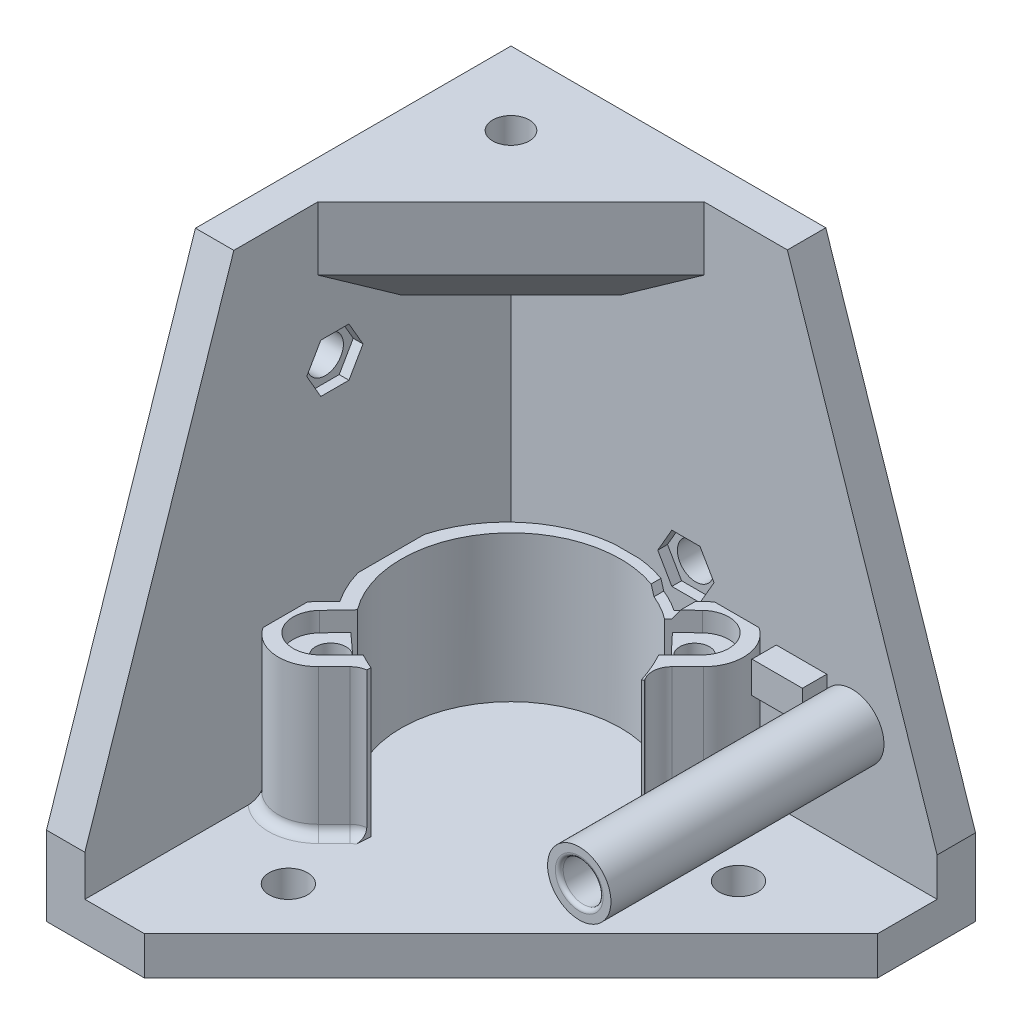
SolidWorks part; units mm, degrees
ref_plane "Front" through (0, 0, 0) normal (0, 0, 1) x (1, 0, 0)
ref_plane "Top" through (0, 0, 0) normal (0, 1, 0) x (1, 0, 0)
ref_plane "Right" through (0, 0, 0) normal (1, 0, 0) x (0, 0, -1)
sketch "Sketch1" plane through (0, 0, 0) normal (0, 1, 0) x (1, 0, 0)
  line L0 (0, 0) -> (0, 60.5)
  line L1 (0, -55) -> (0, 55) construction
  line L2 (0, 60.5) -> (60.5, 60.5)
  line L3 (60.5, 60.5) -> (60.5, 47.75)
  line L4 (60.5, 47.75) -> (12.75, 0)
  line L5 (-55, 0) -> (55, 0) construction
  line L6 (12.75, 0) -> (0, 0)
  dimension "D1" = 60.5
  dimension "D2" = 12.75
extrude "Boss-Extrude1" add sketch "Sketch1" along normal blind 5
sketch "Sketch4" plane through (0, 0, 0) normal (-1, 0, 0) x (0, 0, 1)
  line L0 (-60.5, 5) -> (-60.5, 68.5)
  line L1 (-60.5, 68.5) -> (-19.4, 68.5)
  line L2 (-19.4, 68.5) -> (0, 10.3086)
  line L3 (0, 10.3086) -> (0, 5)
  line L4 (0, -2.75) -> (0, 2.75) construction
  line L5 (-60.5, 5) -> (0, 5) construction
  line L6 (-60.5, 5) -> (0, 5)
  dimension "D1" = 63.5
  dimension "D2" = 41.1
  dimension "D3" = 61.34
extrude "Boss-Extrude2" add sketch "Sketch4" against normal blind 5
sketch "Sketch5" plane through (0, 0, -60.5) normal (0, 0, -1) x (-1, 0, 0)
  line L0 (0, 68.5) -> (-41, 68.5)
  line L1 (-41, 68.5) -> (-60.5, 10.0047)
  line L2 (-60.5, 10.0047) -> (-60.5, 5)
  line L6 (-60.5, 0) -> (0, 0)
  line L7 (0, 0) -> (0, 68.5)
  line L8 (0, 68.5) -> (-5, 68.5)
  line L9 (-5, 68.5) -> (-5, 5)
  line L10 (-5, 5) -> (-60.5, 5)
  line L11 (-60.5, 5) -> (-60.5, 0)
  line L12 (-60.5, 0) -> (0, 0)
  line L13 (0, 0) -> (0, 68.5)
  line L14 (0, 68.5) -> (-5, 68.5)
  line L15 (-5, 68.5) -> (-5, 5)
  line L16 (-5, 5) -> (-60.5, 5)
  line L17 (-60.5, 5) -> (-60.5, 0)
  line M13 (-5, 68.5) -> (-5, 5)
  line M14 (-5, 5) -> (-60.5, 5)
  dimension "D2" = 41
  dimension "D3" = 61.66
  dimension "D1" = 0
extrude "Boss-Extrude3" add sketch "Sketch5" against normal blind 5 contours L1 L2 L0 M14 M13 region at (28.6471, 34.3845, -60.5)
sketch "Sketch6" plane through (0, 5, 0) normal (0, 1, 0) x (1, 0, 0)
  line L0 (60.5, 60.5) -> (0, 60.5) construction
  line L4 (0, 19.4) -> (0, 0)
  line L5 (60.5, 55.5) -> (5, 55.5)
  line L6 (5, 55.5) -> (5, 0)
  line L7 (5, 0) -> (12.75, 0)
  line L8 (12.75, 0) -> (60.5, 47.75)
  line L9 (60.5, 47.75) -> (60.5, 55.5)
  line L10 (60.5, 55.5) -> (5, 55.5)
  line L11 (5, 55.5) -> (5, 0)
  line L12 (5, 0) -> (12.75, 0)
  line L13 (12.75, 0) -> (60.5, 47.75)
  line L14 (60.5, 47.75) -> (60.5, 55.5)
  line L15 (0, 0) -> (5, 0)
  line L16 (5, 0) -> (5, 19.4)
  line L17 (5, 19.4) -> (0, 19.4)
  line L18 (0, 19.4) -> (0, 0)
  line L19 (0, 0) -> (5, 0)
  line L20 (5, 0) -> (5, 19.4)
  line L21 (5, 19.4) -> (0, 19.4)
  line L24 (0, 60.5) -> (0, 19.4)
  line L25 (0, 19.4) -> (5, 19.4)
  line L26 (5, 19.4) -> (5, 55.5)
  line L27 (5, 55.5) -> (41, 55.5)
  line L28 (41, 55.5) -> (41, 60.5)
  line L29 (41, 60.5) -> (0, 60.5)
  line L30 (0, 60.5) -> (0, 19.4)
  line L31 (0, 19.4) -> (5, 19.4)
  line L32 (5, 19.4) -> (5, 55.5)
  line L33 (5, 55.5) -> (41, 55.5)
  line L34 (41, 55.5) -> (41, 60.5)
  line L35 (41, 60.5) -> (0, 60.5)
  circle A0 centre (16.5, 15) radius 2.5
  circle A1 centre (45.5, 44.625) radius 2.5
  dimension "D1" = 5
  dimension "D2" = 5
  dimension "D3" = 0
  dimension "D4" = 15
  dimension "D6" = 16.5
  dimension "D7" = 15
  dimension "D9" = 15.875
  dimension "D5" = 0
  dimension "D8" = 0
extrude "Cut-Extrude1" cut sketch "Sketch6" against normal through all contours A0 | A1 region at (16.5, 5, -15) region at (45.5, 5, -44.625)
sketch "Sketch9" plane through (0, 0, -55.5) normal (0, 0, 1) x (1, 0, 0)
  line L1 (5, 68.5) -> (5, 5) construction
  line L5 (0, 0) -> (60.5, 0)
  line L6 (0, 68.5) -> (0, 0)
  line L7 (41, 68.5) -> (0, 68.5)
  line L8 (60.5, 10.0047) -> (41, 68.5)
  line L9 (60.5, 0) -> (60.5, 10.0047)
  line L10 (0, 0) -> (60.5, 0)
  line L11 (0, 68.5) -> (0, 0)
  line L12 (41, 68.5) -> (0, 68.5)
  line L13 (60.5, 10.0047) -> (41, 68.5)
  line L14 (60.5, 0) -> (60.5, 10.0047)
  line L15 (49.45, 19.0462) -> (49.45, 11.3161) construction
  circle A0 centre (49.45, 19.0462) radius 4.1275
  circle A1 centre (49.45, 19.0462) radius 2.6035
  dimension "D2" = 5.207
  dimension "D3" = 1.524
  dimension "D4" = 49.4538
  dimension "D5" = 44.45
  dimension "D1" = 0
extrude "Boss-Extrude5" add sketch "Sketch9" along normal blind 35.56 contours A1 A0 region at (45.4392, 19.0462, -55.5)
fillet "Fillet1" radius 0.508 1 edges at (52.0535, 19.0462, -19.94)
sketch "Sketch14" plane through (0, 5, 0) normal (0, 1, 0) x (1, 0, 0)
  line L0 (13.4627, 27.5396) -> (14.7681, 26.7924)
  line L1 (12.75, 0) -> (60.5, 47.75) construction
  line L2 (36.625, 23.875) -> (5, 55.5) construction
  line L3 (5, 55.5) -> (60.5, 55.5) construction
  line L4 (32.9604, 47.0373) -> (33.7076, 45.7319)
  line L5 (14.8281, 26.8523) -> (11.8274, 23.8516)
  line L6 (6.723, 28.8027) -> (9.1327, 31.3641)
  line L7 (33.6477, 45.6719) -> (36.6484, 48.6726)
  line L8 (31.6973, 53.777) -> (29.1359, 51.3673)
  line L9 (15.0744, 24.4582) -> (13.006, 22.3898)
  line L10 (5.6561, 29.7396) -> (7.0609, 31.1444)
  line L11 (36.0418, 45.4256) -> (38.1102, 47.494)
  line L12 (30.7604, 54.8439) -> (28.83, 52.9135)
  line L13 (18.1324, 24.8665) -> (30.5234, 17.7734)
  line L14 (35.6335, 42.3676) -> (42.7266, 29.9766)
  line L15 (31.7409, 18.9909) -> (18.852, 25.7543)
  line L16 (41.5091, 28.7591) -> (34.7457, 41.648)
  line L17 (16.5689, 25.6946) -> (16.5343, 25.1798)
  line L18 (34.7457, 41.648) -> (35.7996, 42.0774)
  circle A0 centre (20.5607, 39.9393) radius 14.2875
  arc A1 (11.8274, 23.8516) -> (6.723, 28.8027) centre (9.3129, 26.3661) cw
  arc A2 (36.6484, 48.6726) -> (31.6973, 53.777) centre (34.1339, 51.1871) ccw
  arc A3 (13.006, 22.3898) -> (5.6561, 29.7396) centre (9.3311, 26.0647) cw
  arc A4 (38.1102, 47.494) -> (30.7604, 54.8439) centre (34.4353, 51.1689) ccw
  arc A5 (7.0609, 31.1444) -> (28.83, 52.9135) centre (20.0709, 39.9035) cw
  arc A6 (36.0418, 45.4256) -> (35.6335, 42.3676) centre (37.8378, 43.6295) ccw
  arc A7 (15.0744, 24.4582) -> (18.1324, 24.8665) centre (16.8705, 22.6622) cw
  arc A9 (33.8602, 45.8844) -> (36.3595, 38.5726) centre (13.6025, 34.877) cw
  arc A10 (14.6156, 26.6398) -> (21.9274, 24.1405) centre (25.623, 46.8975) ccw
  point P40 (34.6689, 44.0527)
  point P43 (16.4473, 25.8311)
  line M13 (60.5, 55.5) -> (5, 55.5)
  line M14 (5, 55.5) -> (5, 0)
  line M16 (12.75, 0) -> (60.5, 47.75)
  dimension "D1" = 28.575
  dimension "D2" = 3.556
  dimension "D3" = 2.54
extrude "Boss-Extrude6" add sketch "Sketch14" along normal blind 19.05 contours L2 A0 L5 A1 L6 A5 L10 A3 L9 A7 L13 M16 M14 | L2 L14 A6 L11 A4 L12 A5 A0 L8 A2 L7 M16 M13 region at (7.691, 5, -30.3062) region at (10.0875, 5, -50.8829)
sketch "Sketch15" plane through (0, 68.5, 0) normal (0, 1, 0) x (1, 0, 0)
  line L0 (5, 30.3375) -> (30.1625, 55.5)
  line L1 (0, -33.275) -> (0, 33.275) construction
  line L2 (41, 60.5) -> (0, 60.5) construction
  line L6 (0, 60.5) -> (0, 19.4)
  line L7 (0, 19.4) -> (5, 19.4)
  line L8 (5, 19.4) -> (5, 55.5)
  line L9 (5, 55.5) -> (41, 55.5)
  line L10 (41, 55.5) -> (41, 60.5)
  line L11 (41, 60.5) -> (0, 60.5)
  line L13 (0, 19.4) -> (5, 19.4)
  line L14 (5, 30.3375) -> (5, 55.5)
  line L15 (5, 55.5) -> (30.1625, 55.5)
  line L16 (41, 55.5) -> (41, 60.5)
  circle A0 centre (9.525, 50.975) radius 2.3812
  line M11 (5, 19.4) -> (5, 55.5)
  line M12 (5, 55.5) -> (41, 55.5)
  dimension "D3" = 4.7625
  dimension "D4" = 9.525
  dimension "D5" = 9.525
  dimension "D2" = 45
  dimension "D1" = 0
extrude "Boss-Extrude7" add sketch "Sketch15" against normal blind 15.875 contours L0 A0 M11 M12 region at (13.6178, 68.5, -46.8822)
chamfer "Chamfer2" distance 7.62 angle 45 1 edges at (17.5813, 52.625, -42.9187)
fillet "Fillet2" radius 1.27 7 edges at (39.6065, 5, -51.6871) (37.076, 5, -46.4598) (35.3202, 5, -43.9657) (8.8129, 5, -20.8935) (14.0402, 5, -23.424) (15.745, 5, -24.9392) (35.7165, 5, -42.2225)
sketch "Sketch16" plane through (0, 0, -55.5) normal (0, 0, 1) x (1, 0, 0)
  line L1 (46.1305, 23.2107) -> (38.2864, 23.2107)
  line L2 (46.1305, 23.2107) -> (46.1305, 19.0978)
  line L3 (46.1305, 19.0978) -> (38.2864, 19.0978)
  line L4 (38.2864, 23.2107) -> (38.2864, 19.0978)
extrude "Boss-Extrude8" add sketch "Sketch16" along normal blind 3.175
chamfer "Chamfer3" distance 1.27 angle 45 1 edges at (38.2864, 23.2107, -55.0794)
sketch "Sketch17" plane through (0, 5, 0) normal (0, 1, 0) x (1, 0, 0)
  line L0 (8.716, 30.9212) -> (14.047, 26.0712)
  line L1 (36.625, 23.875) -> (5, 55.5) construction
  line L2 (12.75, 0) -> (60.5, 47.75) construction
  line L3 (5, 55.5) -> (18.418, 55.5) construction
  line L4 (5, 55.5) -> (5, 44.2452) construction
  line L5 (29.6632, 51.8634) -> (34.5959, 46.6202)
  line L22 (37.3079, 55.5) -> (31.5627, 55.5)
  line L23 (30.7604, 54.8439) -> (28.83, 52.9135)
  line L24 (21.7238, 55.5) -> (18.418, 55.5)
  line L25 (5, 44.2452) -> (5, 35.5618)
  line L26 (7.0609, 31.1444) -> (5.6561, 29.7396)
  line L27 (5, 28.9373) -> (5, 23.1921)
  line L28 (13.006, 22.3898) -> (15.0744, 24.4582)
  line L29 (16.5343, 25.1798) -> (16.5689, 25.6946)
  line L30 (16.5343, 25.1798) -> (16.5689, 25.6946)
  line L31 (35.539, 41.9712) -> (35.7996, 42.0774)
  line L32 (35.539, 41.9712) -> (35.7996, 42.0774)
  line L33 (14.6156, 26.6398) -> (11.8274, 23.8516)
  line L34 (6.723, 28.8027) -> (9.1327, 31.3641)
  line L35 (29.1359, 51.3673) -> (31.6973, 53.777)
  line L36 (36.6484, 48.6726) -> (33.8602, 45.8844)
  line L40 (35.7996, 42.0774) -> (35.6335, 42.3676)
  line L41 (36.0418, 45.4256) -> (38.1102, 47.494)
  line L43 (37.3079, 55.5) -> (31.5627, 55.5)
  line L44 (30.7604, 54.8439) -> (28.83, 52.9135)
  line L45 (21.7238, 55.5) -> (18.418, 55.5)
  line L46 (5, 44.2452) -> (5, 35.5618)
  line L47 (7.0609, 31.1444) -> (5.6561, 29.7396)
  line L48 (5, 28.9373) -> (5, 23.1921)
  line L49 (13.006, 22.3898) -> (15.0744, 24.4582)
  line L54 (14.6156, 26.6398) -> (11.8274, 23.8516)
  line L55 (6.723, 28.8027) -> (9.1327, 31.3641)
  line L56 (29.1359, 51.3673) -> (31.6973, 53.777)
  line L57 (36.6484, 48.6726) -> (33.8602, 45.8844)
  line L61 (35.7996, 42.0774) -> (35.6335, 42.3676)
  line L62 (36.0418, 45.4256) -> (38.1102, 47.494)
  circle A1 centre (33.6908, 50.7324) radius 2.1828
  circle A2 centre (10.0204, 27.0078) radius 1.9844
  circle A3 centre (33.6908, 50.7324) radius 1.9288
  arc A15 (38.1102, 47.494) -> (37.3079, 55.5) centre (34.4353, 51.1689) ccw
  arc A17 (31.5627, 55.5) -> (30.7604, 54.8439) centre (34.4353, 51.1689) ccw
  arc A18 (28.83, 52.9135) -> (21.7238, 55.5) centre (20.0709, 39.9035) ccw
  arc A19 (18.418, 55.5) -> (5, 44.2452) centre (20.0709, 39.9035) ccw
  arc A20 (5, 35.5618) -> (7.0609, 31.1444) centre (20.0709, 39.9035) ccw
  arc A21 (5.6561, 29.7396) -> (5, 28.9373) centre (9.3311, 26.0647) ccw
  arc A22 (5, 23.1921) -> (13.006, 22.3898) centre (9.3311, 26.0647) ccw
  arc A23 (16.5343, 25.1798) -> (15.0744, 24.4582) centre (16.8705, 22.6622) ccw
  arc A24 (14.6156, 26.6398) -> (16.5689, 25.6946) centre (25.623, 46.8975) ccw
  arc A25 (6.723, 28.8027) -> (11.8274, 23.8516) centre (9.3129, 26.3661) ccw
  arc A26 (29.1359, 51.3673) -> (9.1327, 31.3641) centre (20.5607, 39.9393) ccw
  arc A27 (36.6484, 48.6726) -> (31.6973, 53.777) centre (34.1339, 51.1871) ccw
  arc A28 (35.539, 41.9712) -> (33.8602, 45.8844) centre (13.6025, 34.877) ccw
  arc A29 (36.0418, 45.4256) -> (35.6335, 42.3676) centre (37.8378, 43.6295) ccw
  arc A30 (38.1102, 47.494) -> (37.3079, 55.5) centre (34.4353, 51.1689) ccw
  arc A32 (31.5627, 55.5) -> (30.7604, 54.8439) centre (34.4353, 51.1689) ccw
  arc A33 (28.83, 52.9135) -> (21.7238, 55.5) centre (20.0709, 39.9035) ccw
  arc A34 (18.418, 55.5) -> (5, 44.2452) centre (20.0709, 39.9035) ccw
  arc A35 (5, 35.5618) -> (7.0609, 31.1444) centre (20.0709, 39.9035) ccw
  arc A36 (5.6561, 29.7396) -> (5, 28.9373) centre (9.3311, 26.0647) ccw
  arc A37 (5, 23.1921) -> (13.006, 22.3898) centre (9.3311, 26.0647) ccw
  arc A38 (16.5343, 25.1798) -> (15.0744, 24.4582) centre (16.8705, 22.6622) ccw
  arc A39 (14.6156, 26.6398) -> (16.5689, 25.6946) centre (25.623, 46.8975) ccw
  arc A40 (6.723, 28.8027) -> (11.8274, 23.8516) centre (9.3129, 26.3661) ccw
  arc A41 (29.1359, 51.3673) -> (9.1327, 31.3641) centre (20.5607, 39.9393) ccw
  arc A42 (36.6484, 48.6726) -> (31.6973, 53.777) centre (34.1339, 51.1871) ccw
  arc A43 (35.539, 41.9712) -> (33.8602, 45.8844) centre (13.6025, 34.877) ccw
  arc A44 (36.0418, 45.4256) -> (35.6335, 42.3676) centre (37.8378, 43.6295) ccw
  line M44 (33.8602, 45.8844) -> (36.6484, 48.6726)
  arc M45 (36.6484, 48.6726) -> (31.6973, 53.777) centre (34.1339, 51.1871) ccw
  line M46 (31.6973, 53.777) -> (29.1359, 51.3673)
  line M48 (9.1327, 31.3641) -> (6.723, 28.8027)
  arc M49 (6.723, 28.8027) -> (11.8274, 23.8516) centre (9.3129, 26.3661) ccw
  line M50 (11.8274, 23.8516) -> (14.6156, 26.6398)
  dimension "D2" = 3.9688
  dimension "D3" = 0.254
  dimension "D1" = 0
extrude "Boss-Extrude9" add sketch "Sketch17" along normal offset from surface (16.51 mm away) 2.54 contours L5 A1 M46 M44 M45 | L0 M48 M49 M50 | A1 L5 A3 region at (11.3737, 5, -28.4876) region at (30.7585, 5, -52.737) region at (33.0584, 5, -52.7569) up to face at (20.9693, 24.05, -39.9839)
sketch "Sketch18" plane through (0, 0, 0) normal (-1, 0, 0) x (0, 0, 1)
  line L0 (-60.5, 68.5) -> (-60.5, 0) construction
  line L1 (33.275, 0) -> (-33.275, 0) construction
  circle A0 centre (-32.56, 49.53) radius 2.3813
  dimension "D1" = 27.94
  dimension "D2" = 49.53
  dimension "D3" = 4.7625
extrude "Cut-Extrude2" cut sketch "Sketch18" against normal up to next
sketch "Sketch19" plane through (0, 0, -60.5) normal (0, 0, -1) x (-1, 0, 0)
  line L0 (0, 33.275) -> (0, -33.275) construction
  line L1 (33.275, 0) -> (-33.275, 0) construction
  circle A0 centre (-27.7812, 26.1937) radius 2.3813
  dimension "D1" = 27.7812
  dimension "D2" = 26.1937
  dimension "D3" = 4.7625
extrude "Cut-Extrude3" cut sketch "Sketch19" against normal up to next
sketch "Sketch20" plane through (0, 0, -55.5) normal (0, 0, 1) x (1, 0, 0)
  line L1 (31.4474, 26.1937) -> (29.6143, 29.3687)
  line L2 (29.6143, 29.3687) -> (25.9482, 29.3687)
  line L3 (25.9482, 29.3687) -> (24.1151, 26.1937)
  line L4 (24.1151, 26.1937) -> (25.9482, 23.0187)
  line L5 (25.9482, 23.0187) -> (29.6143, 23.0187)
  line L6 (29.6143, 23.0187) -> (31.4474, 26.1937)
  circle A0 centre (27.7812, 26.1937) radius 2.3813 construction
  circle A1 centre (27.7812, 26.1937) radius 2.3813
  circle A2 centre (27.7812, 26.1937) radius 3.175 construction
  dimension "D1" = 6.35
extrude "Cut-Extrude4" cut sketch "Sketch20" against normal blind 1.27 and the other way up to vertex (4.1327 mm away) contours L1 L2 L3 L4 L5 L6 other way up to point (29.1359, 24.05, -51.3673)
sketch "Sketch21" plane through (5, 0, 0) normal (1, 0, 0) x (0, 0, -1)
  line L1 (34.3931, 52.705) -> (30.7269, 52.705)
  line L2 (30.7269, 52.705) -> (28.8938, 49.53)
  line L3 (28.8938, 49.53) -> (30.7269, 46.355)
  line L4 (30.7269, 46.355) -> (34.3931, 46.355)
  line L5 (34.3931, 46.355) -> (36.2262, 49.53)
  line L6 (36.2262, 49.53) -> (34.3931, 52.705)
  circle A0 centre (32.56, 49.53) radius 2.3813 construction
  circle A1 centre (32.56, 49.53) radius 2.3812
  circle A2 centre (32.56, 49.53) radius 3.175 construction
  dimension "D1" = 6.35
extrude "Cut-Extrude5" cut sketch "Sketch21" against normal blind 1.27 contours L1 L2 L3 L4 L5 L6
